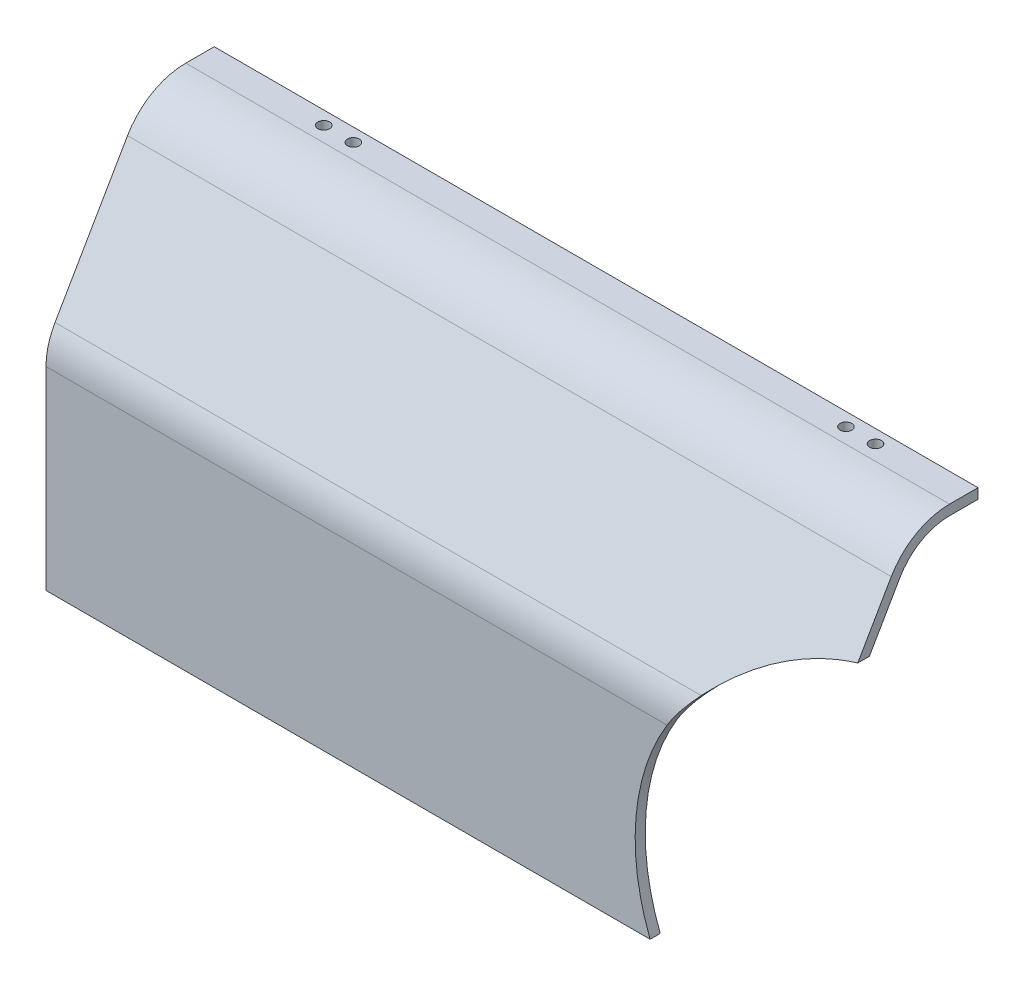
SolidWorks part; units mm, degrees
ref_plane "Alzado" through (0, 0, 0) normal (0, 0, 1) x (1, 0, 0)
ref_plane "Planta" through (0, 0, 0) normal (0, 1, 0) x (1, 0, 0)
ref_plane "Vista lateral" through (0, 0, 0) normal (1, 0, 0) x (0, 0, -1)
sketch "Croquis1" plane through (0, 0, 0) normal (1, 0, 0) x (0, 0, -1)
  line L0 (0, 0) -> (0, 62.1962)
  line L1 (0, 62.1962) -> (28.7321, 111.9615)
  line L2 (28.7321, 111.9615) -> (47, 111.9615)
  line L3 (47, 111.9615) -> (47, 114.9615)
  line L4 (47, 114.9615) -> (27, 114.9615)
  line L5 (27, 114.9615) -> (-3, 63)
  line L6 (-3, 63) -> (-3, 0)
  line L7 (-3, 0) -> (0, 0)
  line L8 (0, 62.1962) -> (29.2398, 62.1962) construction
  dimension "D1" = 3
  dimension "D2" = 3
  dimension "D3" = 3
  dimension "D4" = 63
  dimension "D5" = 60
  dimension "D6" = 20
  dimension "D7" = 60
extrude "Saliente-Extruir1" add sketch "Croquis1" along normal mid plane 227
fillet "Redondeo1" radius 20 1 edges at (0, 63, 3)
fillet "Redondeo2" radius 20 1 edges at (0, 114.9615, -27)
fillet "Redondeo3" radius 17 1 edges at (0, 111.9615, -28.7321)
fillet "Redondeo4" radius 17 1 edges at (0, 62.1962, 0)
sketch "Croquis2" plane through (0, 0, 3) normal (0, 0, 1) x (1, 0, 0)
  circle A0 centre (126.88, 18.7215) radius 70
  dimension "D1" = 140
  dimension "D2" = 13.38
  dimension "D3" = 86.24
extrude "Cortar-Extruir1" [suppressed] cut sketch "Croquis2" against normal through all
sketch "Croquis4" plane through (0, 114.9615, 0) normal (0, 1, 0) x (1, 0, 0)
  circle A0 centre (-77, 43.047) radius 1.75
  circle A1 centre (-68.2, 43.047) radius 1.75
extrude "Cortar-Extruir3" cut sketch "Croquis4" against normal blind 4
sketch "Croquis5" plane through (0, 114.9615, 0) normal (0, 1, 0) x (1, 0, 0)
  circle A0 centre (78.2, 43.047) radius 1.75
  circle A1 centre (87, 43.047) radius 1.75
  dimension "D1" = 3.5
extrude "Cortar-Extruir4" cut sketch "Croquis5" against normal blind 4
sketch "Croquis6" plane through (0, 0, 3) normal (0, 0, 1) x (1, 0, 0)
  circle A0 centre (126.9781, 23.7215) radius 65.3765
extrude "Cortar-Extruir5" cut sketch "Croquis6" against normal blind 20
